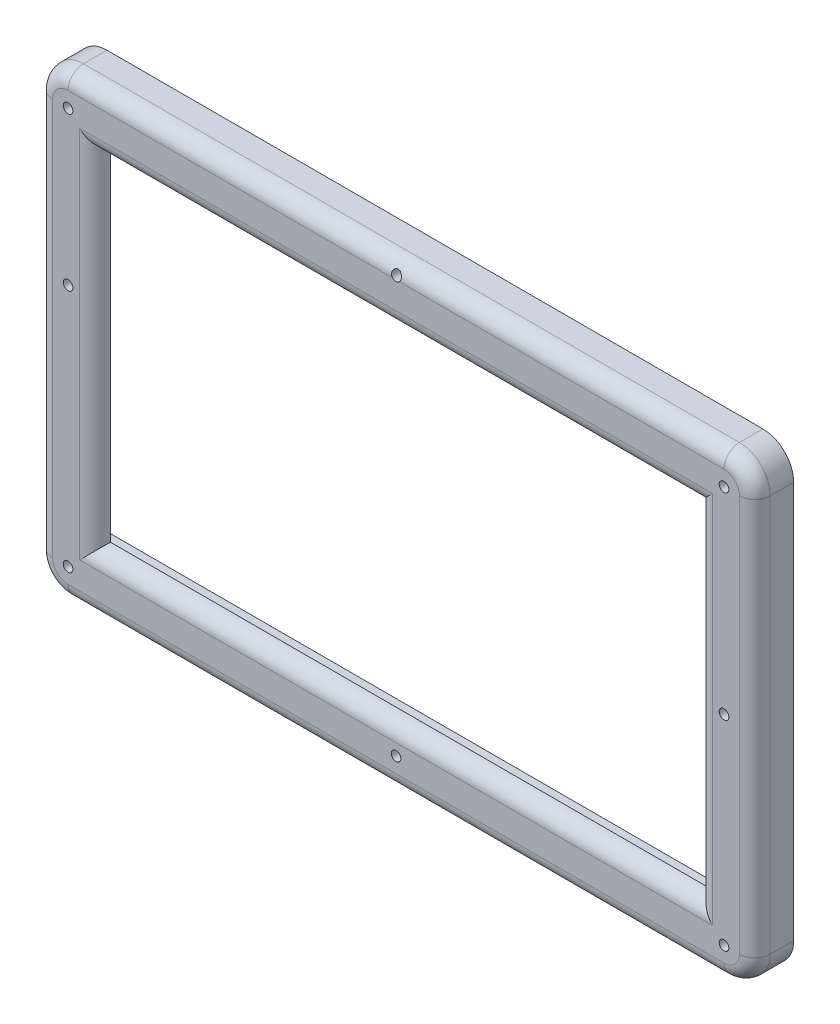
SolidWorks part; units mm, degrees
ref_plane "Front Plane" through (0, 0, 0) normal (0, 0, 1) x (1, 0, 0)
ref_plane "Top Plane" through (0, 0, 0) normal (0, 1, 0) x (1, 0, 0)
ref_plane "Right Plane" through (0, 0, 0) normal (1, 0, 0) x (0, 0, -1)
sketch "Sketch1" plane through (0, 0, 0) normal (0, 0, 1) x (1, 0, 0)
  line L0 (-89.2392, 36.736) -> (-89.2392, -64.384)
  line L1 (-83.1292, 28.926) -> (73.3008, 28.926)
  line L2 (-83.1292, 28.926) -> (-83.1292, -60.224)
  line L3 (-83.1292, -60.224) -> (73.3008, -60.224)
  line L4 (73.3008, 28.926) -> (73.3008, -60.224)
  line L5 (-88.7392, 36.236) -> (76.1808, 36.236)
  line L6 (-88.7392, 36.236) -> (-88.7392, -63.884)
  line L7 (-88.7392, -63.884) -> (76.1808, -63.884)
  line L8 (76.1808, 36.236) -> (76.1808, -63.884)
  line L9 (-89.2392, -64.384) -> (76.6808, -64.384)
  line L10 (76.6808, 36.736) -> (76.6808, -64.384)
  line L11 (-89.2392, 36.736) -> (76.6808, 36.736)
  line L12 (-98.1292, 35.926) -> (-98.1292, -67.224)
  line L13 (-90.1292, -75.224) -> (80.3008, -75.224)
  line L14 (88.3008, 35.926) -> (88.3008, -67.224)
  line L15 (-90.1292, 43.926) -> (80.3008, 43.926)
  line L16 (-98.1292, 43.926) -> (-98.1292, -75.224) construction
  line L17 (-98.1292, 43.926) -> (88.3008, 43.926) construction
  line L18 (-98.1292, -75.224) -> (88.3008, -75.224) construction
  line L19 (88.3008, 43.926) -> (88.3008, -75.224) construction
  arc A0 (-98.1292, 35.926) -> (-90.1292, 43.926) centre (-90.1292, 35.926) cw
  arc A1 (-90.1292, -75.224) -> (-98.1292, -67.224) centre (-90.1292, -67.224) cw
  arc A2 (88.3008, -67.224) -> (80.3008, -75.224) centre (80.3008, -67.224) cw
  arc A3 (80.3008, 43.926) -> (88.3008, 35.926) centre (80.3008, 35.926) cw
  circle A4 centre (80.3008, 35.926) radius 1.25
  circle A5 centre (80.3008, -67.224) radius 1.25
  circle A6 centre (-90.1292, -67.224) radius 1.25
  circle A7 centre (-90.1292, 35.926) radius 1.25
  dimension "D9" = 8
  dimension "D10" = 8
  dimension "D11" = 8
  dimension "D12" = 8
  dimension "D13" = 2.5
  dimension "D14" = 2.5
  dimension "D15" = 2.5
  dimension "D16" = 2.5
  dimension "D1" = 89.15
  dimension "D2" = 156.43
  dimension "D3" = 164.92
  dimension "D4" = 100.12
  dimension "D5" = 3.66
  dimension "D6" = 5.61
  dimension "D7" = 0.5
  dimension "D8" = 15
extrude "Boss-Extrude1" add sketch "Sketch1" along normal blind 4 contours A3 L15 A0 L12 A1 L13 A2 L14 L0 L11 L10 L9 | L11 L0 L9 L10 L5 L8 L7 L6 | L8 L5 L6 L7 L1 L4 L3 L2 region at (-88.7929, 35.3779, 0) region at (-6.2792, 34.3067, 0) region at (-94.2215, 40.0184, 0)
extrude "Boss-Extrude2" add sketch "Sketch1<3>" against normal blind 6.1 contours A3 L15 A0 L12 A1 L13 A2 L14 L0 L11 L10 L9 region at (-94.2215, 40.0184, 0)
sketch "Sketch1<3>" plane through (0, 0, 0) normal (0, 0, 1) x (1, 0, 0) same geometry as "Sketch1"
fillet "Fillet1" radius 4 12 edges at (-95.786, 41.5829, 4) (-4.9142, 43.926, 4) (85.9577, 41.5829, 4) (88.3008, -15.649, 4) (85.9577, -72.8808, 4) (-4.9142, -75.224, 4) (-95.786, -72.8808, 4) (-4.9142, -60.224, 4) (-4.9142, 28.926, 4) (-83.1292, -15.649, 4) (73.3008, -15.649, 4) (-98.1292, -15.649, 4)
sketch "Sketch2" plane through (0, 36.736, 0) normal (0, -1, 0) x (1, 0, 0)
  line L0 (-89.1771, -6.1) -> (76.6808, -6.1) construction
  line L1 (-38.9092, -6.1) -> (-21.7192, -6.1)
  line L2 (-38.9092, -6.1) -> (-38.9092, 0)
  line L3 (-38.9092, 0) -> (-21.7192, 0)
  line L4 (-21.7192, -6.1) -> (-21.7192, 0)
  line L5 (-89.1771, 0) -> (76.6808, 0) construction
  line L6 (-89.2392, -6.1) -> (-89.2392, 0) construction
  dimension "D1" = 50.33
  dimension "D2" = 67.52
extrude "Cut-Extrude1" cut sketch "Sketch2" against normal blind 1
sketch "Sketch3" plane through (76.6808, 0, 0) normal (-1, 0, 0) x (0, 0, 1)
  line L0 (-6.1, 36.736) -> (-6.1, -64.384) construction
  line L1 (-6.1, -10.624) -> (0, -10.624)
  line L2 (-6.1, -10.624) -> (-6.1, -22.594)
  line L3 (-6.1, -22.594) -> (0, -22.594)
  line L4 (0, -10.624) -> (0, -22.594)
  line L5 (0, 36.736) -> (0, -64.384) construction
  line L6 (-6.1, 36.736) -> (0, 36.736) construction
  dimension "D1" = 47.36
  dimension "D2" = 11.97
extrude "Cut-Extrude2" cut sketch "Sketch3" against normal blind 1
sketch "Sketch4" plane through (0, 0, -6.1) normal (0, 0, -1) x (-1, 0, 0)
  line L0 (90.1292, 43.926) -> (-80.3008, 43.926) construction
  line L1 (-88.3008, 35.926) -> (-88.3008, -67.224) construction
  line L2 (90.1292, -75.224) -> (-80.3008, -75.224) construction
  line L3 (98.1292, 35.926) -> (98.1292, -67.224) construction
  circle A0 centre (4.9092, 40.776) radius 1.25
  circle A1 centre (-80.3008, -15.244) radius 1.25
  circle A2 centre (4.9092, -67.224) radius 1.25
  circle A3 centre (90.1292, -3.884) radius 1.25
  dimension "D1" = 2.5
  dimension "D2" = 2.5
  dimension "D3" = 2.5
  dimension "D4" = 2.5
  dimension "D5" = 3.15
  dimension "D6" = 8
  dimension "D7" = 8
  dimension "D8" = 8
  dimension "D9" = 59.98
  dimension "D10" = 93.22
  dimension "D11" = 47.81
extrude "Cut-Extrude3" cut sketch "Sketch4" against normal through all
